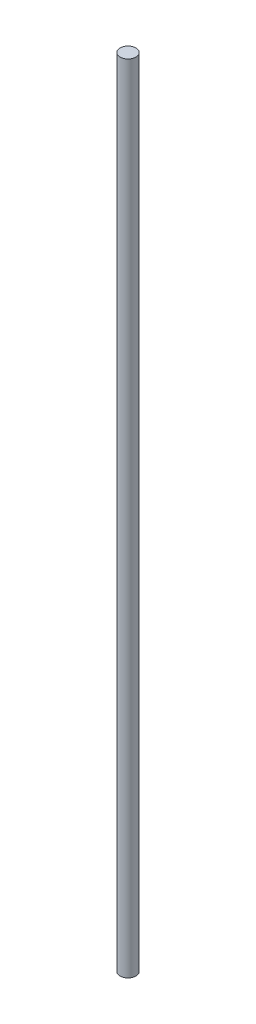
SolidWorks part; units mm, degrees
ref_plane "Front Plane" through (0, 0, 0) normal (0, 0, 1) x (1, 0, 0)
ref_plane "Top Plane" through (0, 0, 0) normal (0, 1, 0) x (1, 0, 0)
ref_plane "Right Plane" through (0, 0, 0) normal (1, 0, 0) x (0, 0, -1)
ref_axis "Axis1" through (0, 155, 0) along (0, -1, 0)
sketch "Sketch2" plane through (0, 0, 0) normal (0, 0, 1) x (1, 0, 0)
  line L1 (0, 0) -> (4, 0)
  line L2 (0, 0) -> (0, 400)
  line L3 (0, 400) -> (4, 400)
  line L4 (4, 0) -> (4, 400)
  dimension "D1" = 4
  dimension "length" = 400
revolve "Revolve1" add sketch "Sketch2" angle 360 about L2
sketch "Sketch3" plane through (0, 0, 0) normal (0, -1, 0) x (1, 0, 0)
  circle A0 centre (0, 0) radius 4
  circle A1 centre (0, 0) radius 4 construction
curve "Helix/Spiral1" pitch 2 height 400 turns 200 parameters "length"=400
ref_plane "Plane1" through (0, 0, -4) normal (-0.9968, 0.0793, 0) x (0, 0, 1)
sketch "Sketch4" plane through (0, 0, -4) normal (-0.9968, 0.0793, 0) x (0, 0, 1)
  line L1 (-0.5, 0.5) -> (0.5, 0.5)
  line L2 (-0.5, 0.5) -> (-0.5, -0.5)
  line L3 (-0.5, -0.5) -> (0.5, -0.5)
  line L4 (0.5, 0.5) -> (0.5, -0.5)
  line L5 (-0.5, 0.5) -> (0.5, -0.5) construction
  line L6 (-0.5, -0.5) -> (0.5, 0.5) construction
  point P0 (0, 0)
  dimension "D1" = 1
sweep "Cut-Sweep1" [suppressed] cut profiles "Sketch4" path "Helix/Spiral1"
